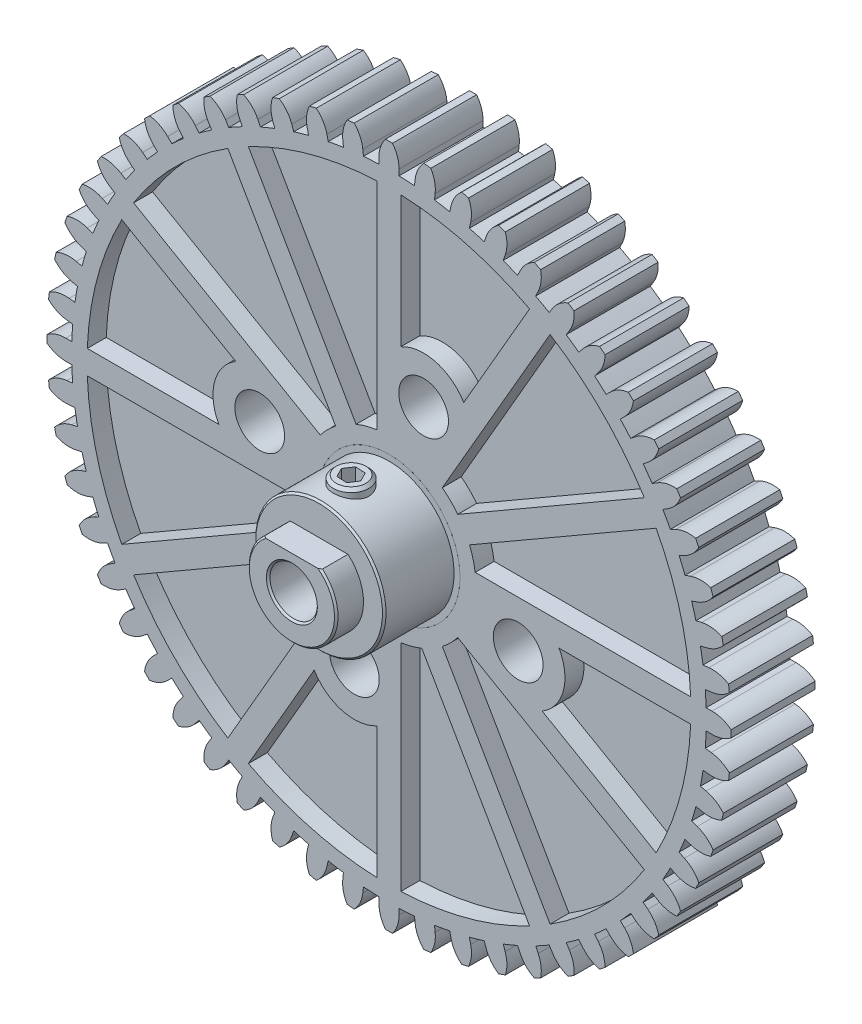
SolidWorks part; units mm, degrees
material "PA Type 6"
material "1060 Alloy"
material "Plain Carbon Steel"
material "PA Type 6"
ref_plane "Front Plane" through (0, 0, 0) normal (0, 0, 1) x (1, 0, 0)
ref_plane "Top Plane" through (0, 0, 0) normal (0, 1, 0) x (1, 0, 0)
ref_plane "Right Plane" through (0, 0, 0) normal (1, 0, 0) x (0, 0, -1)
ref_axis "Axis1" through (0, 0, -11.7513) along (0, 0, 1)
sketch "Sketch4" plane through (0, 0, 0) normal (0, 1, 0) x (1, 0, 0)
  line L0 (0, 23.226) -> (0, -37.2777) construction
  line L1 (2, 0.5) -> (2, -15.3)
  line L2 (2, -15.3) -> (3.75, -15.3)
  line L3 (3.75, -15.3) -> (3.75, -13)
  line L4 (3.75, -13) -> (5.5, -13)
  line L5 (5.5, -13) -> (5.5, -7.1)
  line L6 (5.5, -7.1) -> (6, -7.1)
  line L7 (6, -7.1) -> (6, 0)
  line L8 (6, 0) -> (5.5, 0)
  line L9 (5.5, 0) -> (5.5, 0.5)
  line L10 (5.5, 0.5) -> (2, 0.5)
  dimension "D1" = 4
  dimension "D2" = 11
  dimension "D3" = 12
  dimension "D4" = 7.5
  dimension "D5" = 0.5
  dimension "D6" = 7.1
  dimension "D7" = 15.8
  dimension "D8" = 13.5
revolve "Revolve1" add sketch "Sketch4" angle 360 about L0
sketch "Sketch5" plane through (0, 0, 0) normal (0, 1, 0) x (1, 0, 0)
  line L0 (0, 11.7513) -> (0, -13.6828) construction
  line L1 (-3.75, -15.3) -> (3.75, -15.3) construction
  circle A0 centre (0, -10.3) radius 1.25
  dimension "D2" = 2.5
  dimension "D1" = 5
extrude "Cut-Extrude1" cut sketch "Sketch5" along normal through all
sketch "Sketch6" plane through (0, 0, 13) normal (0, 0, 1) x (1, 0, 0)
  line L1 (2.4372, 4.65) -> (-2.4372, 4.65)
  line L2 (2.4372, 4.65) -> (2.4372, 2.85)
  line L3 (2.4372, 2.85) -> (-2.4372, 2.85)
  line L4 (-2.4372, 4.65) -> (-2.4372, 2.85)
  line L5 (2.4372, 4.65) -> (-2.4372, 2.85) construction
  line L6 (2.4372, 2.85) -> (-2.4372, 4.65) construction
  circle A0 centre (0, 0) radius 3.75 construction
  circle A1 centre (0, 0) radius 3.75 construction
  point P0 (0, 3.75)
  dimension "D1" = 6.6
extrude "Cut-Extrude2" cut sketch "Sketch6" along normal through all
sketch "Sketch1" plane through (0, 0, 0) normal (0, 0, 1) x (1, 0, 0)
  circle A0 centre (0, 0) radius 26.8
  circle A1 centre (0, 0) radius 6
  dimension "D1" = 53.6
  dimension "D2" = 12
extrude "Boss-Extrude1" add sketch "Sketch1" along normal blind 7.1 separate body
sketch "Sketch2" plane through (0, 0, 0) normal (0, 0, 1) x (1, 0, 0)
  line L0 (0, 19.1132) -> (0, -4.5821) construction
  line L1 (0.85, 26.7865) -> (0.85, 27.2865)
  line L2 (-0.85, 26.7865) -> (-0.85, 27.2865)
  line L3 (-0.85, 26.7865) -> (0.85, 26.7865)
  circle A0 centre (0, 0) radius 28.9 construction
  arc A1 (-0.3, 28.8984) -> (0.3, 28.8984) centre (0, 0) cw
  circle A2 centre (0, 0) radius 26.8 construction
  arc A3 (0.85, 27.2865) -> (0.3, 28.8984) centre (-1.7871, 27.2865) ccw
  arc A4 (-0.85, 27.2865) -> (-0.3, 28.8984) centre (1.7871, 27.2865) cw
  dimension "D1" = 57.8
  dimension "D2" = 0.6
  dimension "D3" = 1.7
  dimension "D4" = 0.5
extrude "Boss-Extrude2" add sketch "Sketch2" along normal up to surface (7.1 mm away) contours A3 A1 A4 L2 L3 L1 up to face at (26.8, 0, 7.1)
pattern_circular "CirPattern1" count 56 over 360 about axis through (0, 0, -11.7513) along (0, 0, 1) of "Boss-Extrude2"
sketch "Sketch7" plane through (0, 0, 7.1) normal (0, 0, 1) x (1, 0, 0)
  line L0 (0, 0) -> (0, 31.5134) construction
  line L1 (11.8742, 22.5667) -> (2.7748, 6.8061)
  line L2 (16.1025, 27.8904) -> (0, 0) construction
  line L3 (1, 7.2817) -> (1, 25.4804)
  line L4 (1, 3.7321) -> (1, 31.5134) construction
  line L5 (15.2365, 28.3904) -> (1, 3.7321) construction
  arc A0 (2.7748, 6.8061) -> (1, 7.2817) centre (0, 0) ccw
  arc A1 (11.8742, 22.5667) -> (1, 25.4804) centre (0, 0) ccw
  circle A2 centre (0, 0) radius 7.35 construction
  circle A3 centre (0, 0) radius 25.5 construction
  dimension "D2" = 14.7
  dimension "D3" = 51
  dimension "D1" = 30
  dimension "D4" = 1
extrude "Cut-Extrude3" cut sketch "Sketch7" against normal blind 1.6
sketch "Sketch8" plane through (0, 0, 0) normal (0, 0, -1) x (-1, 0, 0)
  line L2 (-11.8742, 22.5667) -> (-2.7748, 6.8061)
  line L3 (-1, 7.2817) -> (-1, 25.4804)
  line L4 (-11.8742, 22.5667) -> (-2.7748, 6.8061)
  line L5 (-1, 7.2817) -> (-1, 25.4804)
  arc A2 (-1, 7.2817) -> (-2.7748, 6.8061) centre (0, 0) ccw
  arc A3 (-1, 25.4804) -> (-11.8742, 22.5667) centre (0, 0) ccw
  arc A4 (-1, 7.2817) -> (-2.7748, 6.8061) centre (0, 0) ccw
  arc A5 (-1, 25.4804) -> (-11.8742, 22.5667) centre (0, 0) ccw
  dimension "D1" = 0
extrude "Cut-Extrude4" cut sketch "Sketch8" against normal blind 1.6
pattern_circular "CirPattern2" count 12 over 360 about axis through (0, 0, -11.7513) along (0, 0, 1) of "Cut-Extrude4", "Cut-Extrude3"
sketch "Sketch9" plane through (0, 0, 7.1) normal (0, 0, 1) x (1, 0, 0)
  line L0 (0, 0) -> (9.141, 34.1146) construction
  line L1 (0, 34.0333) -> (0, -36.5108) construction
  line L2 (1, 25.4804) -> (1, 7.2817) construction
  line L3 (2.7748, 6.8061) -> (11.8742, 22.5667) construction
  line L4 (1, 14.3643) -> (1, 7.2817)
  line L5 (2.7748, 6.8061) -> (6.3161, 12.9399)
  circle A0 centre (0, 0) radius 11.3 construction
  circle A1 centre (0, 0) radius 15.25 construction
  arc A3 (2.7748, 6.8061) -> (1, 7.2817) centre (0, 0) ccw construction
  arc A4 (2.7748, 6.8061) -> (1, 7.2817) centre (0, 0) ccw
  arc A5 (6.3161, 12.9399) -> (1, 14.3643) centre (2.9247, 10.915) ccw
  dimension "D1" = 22.6
  dimension "D3" = 30.5
  dimension "D2" = 15
extrude "Boss-Extrude3" add sketch "Sketch9" against normal up to surface (7.1 mm away) up to face at (11.4928, 11.4928, 0)
sketch "Sketch10" plane through (0, 0, 7.1) normal (0, 0, 1) x (1, 0, 0)
  circle A0 centre (2.9247, 10.915) radius 2.1
  dimension "D1" = 4.2
extrude "Cut-Extrude5" cut sketch "Sketch10" against normal through all
pattern_circular "CirPattern3" count 4 over 360 about axis through (0, 0, -11.7513) along (0, 0, 1) of "Boss-Extrude3", "Cut-Extrude5"
ref_plane "Plane1" through (0, 1.5, 0) normal (0, 1, 0) x (1, 0, 0)
sketch "Sketch12" plane through (0, 1.5, 0) normal (0, 1, 0) x (1, 0, 0)
  circle A0 centre (0, -10.3) radius 1.5
  dimension "D1" = 3
extrude "Boss-Extrude4" add sketch "Sketch12" along normal blind 4.6 separate body
chamfer "Chamfer1" distance 0.25 angle 45 1 edges at (0, 6.1, 11.8)
sketch "Sketch13" plane through (0, 6.1, 0) normal (0, 1, 0) x (1, 0, 0)
  line L1 (0.3895, -11.0735) -> (0.8646, -10.3494)
  line L2 (0.8646, -10.3494) -> (0.4751, -9.5759)
  line L3 (0.4751, -9.5759) -> (-0.3895, -9.5265)
  line L4 (-0.3895, -9.5265) -> (-0.8646, -10.2506)
  line L5 (-0.8646, -10.2506) -> (-0.4751, -11.0241)
  line L6 (-0.4751, -11.0241) -> (0.3895, -11.0735)
  circle A0 centre (0, -10.3) radius 0.75 construction
  dimension "D1" = 1.5
extrude "Cut-Extrude6" cut sketch "Sketch13" against normal blind 2
chamfer "Chamfer2" distance 0.15 angle 45 5 edges at (-2, 0, 15.3) (-2, 0, -0.5) (-5.5, 0, -0.5) (0, -3.75, 15.3) (-5.5, 0, 13)
